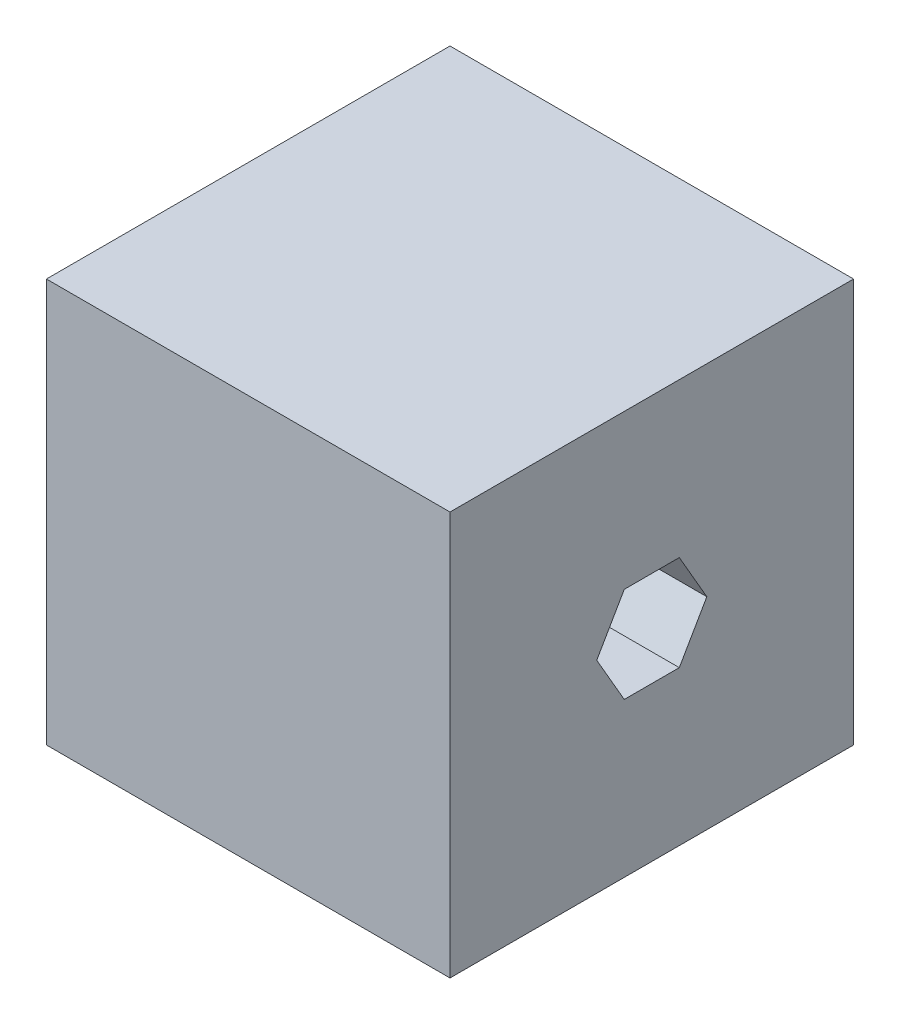
SolidWorks part; units mm, degrees
ref_plane "Front Plane" through (0, 0, 0) normal (0, 0, 1) x (1, 0, 0)
ref_plane "Top Plane" through (0, 0, 0) normal (0, 1, 0) x (1, 0, 0)
ref_plane "Right Plane" through (0, 0, 0) normal (1, 0, 0) x (0, 0, -1)
sketch "Sketch2" plane through (0, 0, 0) normal (0, 1, 0) x (1, 0, 0)
  line L1 (-25.4, -25.4) -> (25.4, -25.4)
  line L2 (-25.4, -25.4) -> (-25.4, 25.4)
  line L3 (-25.4, 25.4) -> (25.4, 25.4)
  line L4 (25.4, -25.4) -> (25.4, 25.4)
  line L5 (-25.4, -25.4) -> (25.4, 25.4) construction
  line L6 (-25.4, 25.4) -> (25.4, -25.4) construction
  point P0 (0, 0)
  dimension "D1" = 50.8
  dimension "D2" = 50.8
extrude "Boss-Extrude1" add sketch "Sketch2" along normal blind 50.8
sketch "Sketch3" plane through (0, 0, 0) normal (0, -1, 0) x (1, 0, 0)
  line L1 (-11.176, 11.176) -> (11.176, 11.176)
  line L2 (-11.176, 11.176) -> (-11.176, -11.176)
  line L3 (-11.176, -11.176) -> (11.176, -11.176)
  line L4 (11.176, 11.176) -> (11.176, -11.176)
  line L5 (-11.176, 11.176) -> (11.176, -11.176) construction
  line L6 (-11.176, -11.176) -> (11.176, 11.176) construction
  line L7 (-12.7, 12.7) -> (12.7, 12.7)
  line L8 (-12.7, 12.7) -> (-12.7, -12.7)
  line L9 (-12.7, -12.7) -> (12.7, -12.7)
  line L10 (12.7, 12.7) -> (12.7, -12.7)
  line L11 (-12.7, 12.7) -> (12.7, -12.7) construction
  line L12 (-12.7, -12.7) -> (12.7, 12.7) construction
  point P0 (0, 0)
  point P6 (0, 0)
  dimension "D1" = 22.352
  dimension "D2" = 22.352
  dimension "D3" = 25.4
  dimension "D4" = 25.4
extrude "Cut-Extrude1" cut sketch "Sketch3" against normal blind 15.24
sketch "Sketch4" plane through (25.4, 0, 0) normal (1, 0, 0) x (0, 0, -1)
  line L1 (6.9282, 25.4) -> (3.4641, 31.4)
  line L2 (3.4641, 31.4) -> (-3.4641, 31.4)
  line L3 (-3.4641, 31.4) -> (-6.9282, 25.4)
  line L4 (-6.9282, 25.4) -> (-3.4641, 19.4)
  line L5 (-3.4641, 19.4) -> (3.4641, 19.4)
  line L6 (3.4641, 19.4) -> (6.9282, 25.4)
  line L7 (-25.4, 50.8) -> (25.4, 50.8) construction
  line L8 (25.4, 50.8) -> (25.4, 0) construction
  circle A0 centre (0, 25.4) radius 6 construction
  dimension "D1" = 12
  dimension "D2" = 25.4
  dimension "D3" = 25.4
extrude "Cut-Extrude2" cut sketch "Sketch4" against normal blind 38.1
